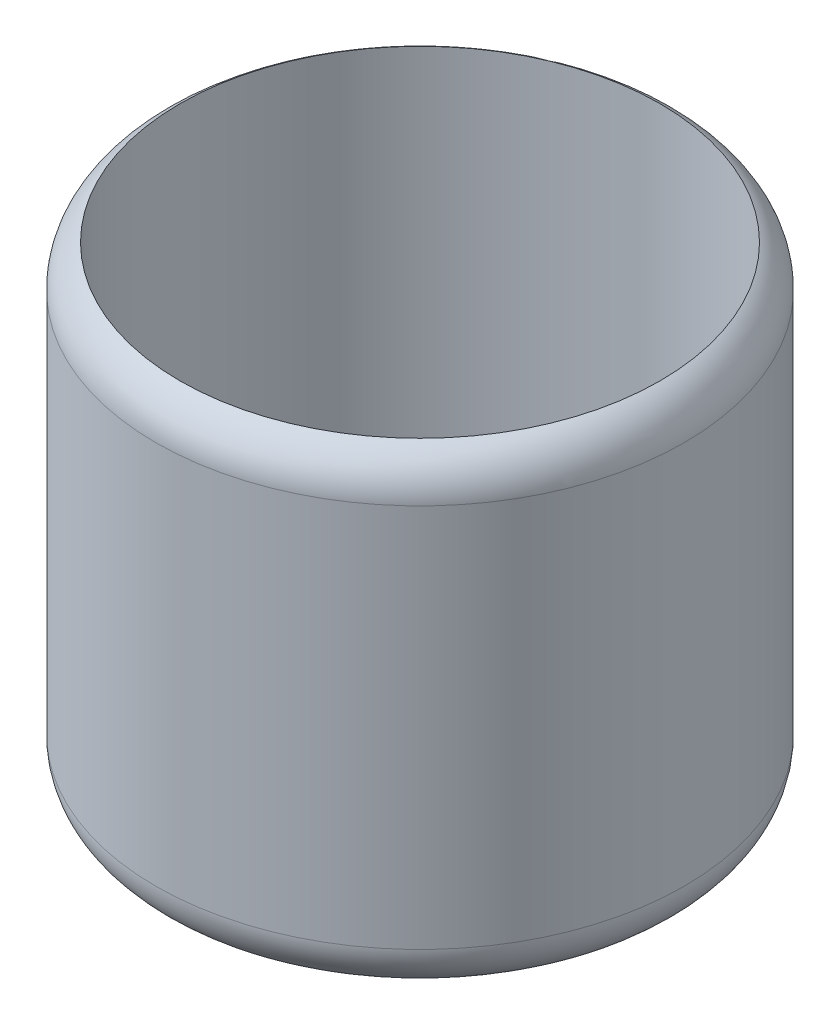
SolidWorks part; units mm, degrees
ref_plane "Front" through (0, 0, 0) normal (0, 0, 1) x (1, 0, 0)
ref_plane "Top" through (0, 0, 0) normal (0, 1, 0) x (1, 0, 0)
ref_plane "Right" through (0, 0, 0) normal (1, 0, 0) x (0, 0, -1)
sketch "Sketch1" plane through (0, 0, 0) normal (0, 1, 0) x (1, 0, 0)
  circle A0 centre (0, 0) radius 55
  dimension "D1" = 110
extrude "Boss-Extrude1" add sketch "Sketch1" along normal blind 100
fillet "Fillet1" radius 10 2 edges at (0, 0, 55) (0, 100, 55)
sketch "Sketch3" plane through (0, 100, 0) normal (0, 1, 0) x (1, 0, 0)
  circle A0 centre (0, 0) radius 50
extrude "Cut-Extrude1" cut sketch "Sketch3" against normal blind 90
ref_axis "Axis1" through (0, 90, 0) along (0, -1, 0)
sketch "Sketch5" plane through (0, 0, 0) normal (1, 0, 0) x (0, 0, -1)
  line L0 (-55, 90) -> (-55, 10) construction
  point P0 (-30, 15)
  point P1 (-10, 15)
  point P2 (10, 15)
  point P3 (30, 15)
  dimension "D1" = 20
  dimension "D2" = 20
  dimension "D3" = 20
  dimension "D4" = 15
  dimension "D5" = 25
